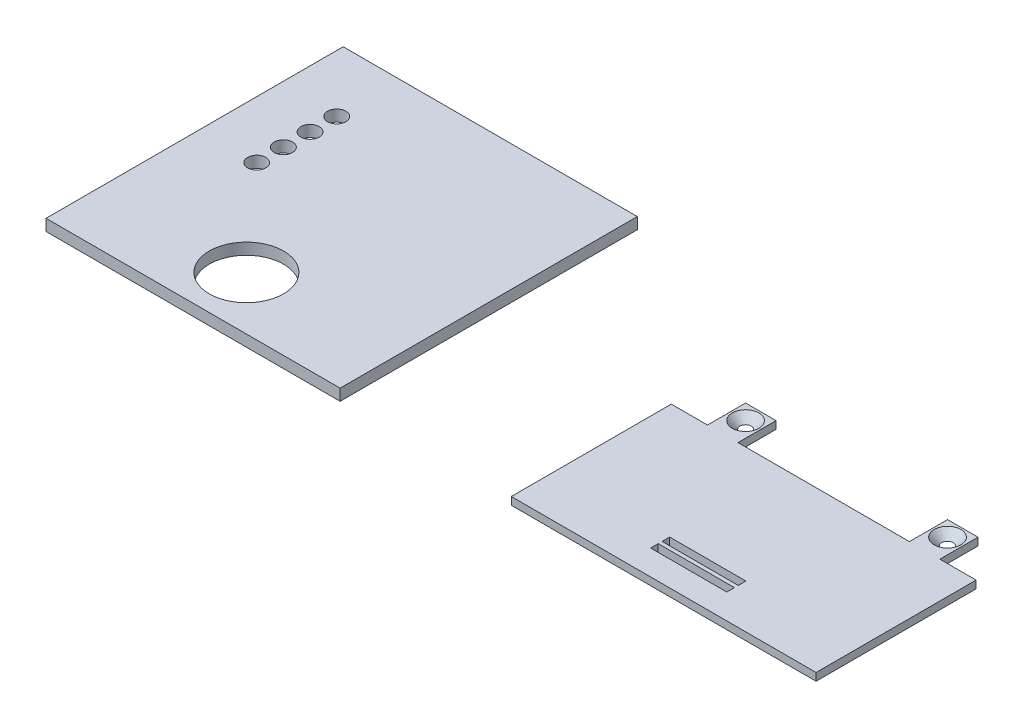
SolidWorks part; units mm, degrees
ref_plane "Front" through (0, 0, 0) normal (0, 0, 1) x (1, 0, 0)
ref_plane "Top" through (0, 0, 0) normal (0, 1, 0) x (1, 0, 0)
ref_plane "Right" through (0, 0, 0) normal (1, 0, 0) x (0, 0, -1)
sketch "Эскиз1" plane through (0, 0, 0) normal (0, 1, 0) x (1, 0, 0)
  line L1 (-158.1764, 86.5492) -> (-80.9764, 86.5492)
  line L2 (-158.1764, 86.5492) -> (-158.1764, 8.5492)
  line L3 (-158.1764, 8.5492) -> (-80.9764, 8.5492)
  line L4 (-80.9764, 86.5492) -> (-80.9764, 8.5492)
  dimension "D1" = 77.2
  dimension "D2" = 78
extrude "Бобышка-Вытянуть1" add sketch "Эскиз1" along normal blind 3
sketch "Эскиз2" plane through (0, 3, 0) normal (0, 1, 0) x (1, 0, 0)
  line L0 (-158.1764, 86.5492) -> (-158.1764, 8.5492) construction
  line L1 (-158.1764, 8.5492) -> (-80.9764, 8.5492) construction
  circle A0 centre (-119.5764, 22.5492) radius 9.75
  dimension "D1" = 38.6
  dimension "D2" = 14
extrude "Вырез-Вытянуть1" cut sketch "Эскиз2" along normal blind 87 and the other way blind 71
sketch "Эскиз3" plane through (0, 3, 0) normal (0, 1, 0) x (1, 0, 0)
  line L0 (-158.1764, 86.5492) -> (-158.1764, 8.5492) construction
  circle A0 centre (-143.1764, 48.8556) radius 2.4
  circle A1 centre (-143.1764, 55.8556) radius 2.4
  circle A2 centre (-138.1048, 0) radius 2.4
  circle A3 centre (-138.1048, 0) radius 2.4
  circle A4 centre (-143.1764, 69.8556) radius 2.4
  circle A5 centre (-143.1764, 62.8556) radius 2.4
  point P14 (0, 0)
  dimension "D1" = 15
  dimension "D2" = 15
  dimension "D3" = 7
  dimension "D4" = 15
  dimension "D5" = 7
  dimension "D6" = 15
  dimension "D7" = 7
extrude "Вырез-Вытянуть3" cut sketch "Эскиз3" against normal blind 207 and the other way blind 150 contours A4 | A5 | A1 | A0
sketch "Эскиз4" plane through (0, 0, 0) normal (0, 1, 0) x (1, 0, 0)
  line L1 (-36.8822, 61.3775) -> (43.1178, 61.3775)
  line L2 (-36.8822, 61.3775) -> (-36.8822, 9.3775)
  line L3 (-36.8822, 9.3775) -> (43.1178, 9.3775)
  line L4 (43.1178, 61.3775) -> (43.1178, 9.3775)
  dimension "D1" = 80
  dimension "D2" = 52
extrude "Бобышка-Вытянуть2" add sketch "Эскиз4" against normal blind 2 separate body
sketch "Эскиз5" plane through (0, 0, 0) normal (0, 1, 0) x (1, 0, 0)
  line L1 (-36.8822, 61.3775) -> (-27.3822, 61.3775)
  line L2 (-36.8822, 61.3775) -> (-36.8822, 51.3775)
  line L3 (-36.8822, 51.3775) -> (-27.3822, 51.3775)
  line L4 (-27.3822, 61.3775) -> (-27.3822, 51.3775)
  point P5 (-27.3822, 56.3775)
  dimension "D1" = 9.5
  dimension "D2" = 10
extrude "Вырез-Вытянуть4" cut sketch "Эскиз5" along normal blind 35 and the other way blind 32
sketch "Эскиз6" plane through (0, 0, 0) normal (0, 1, 0) x (1, 0, 0)
  line L0 (43.1178, 61.3775) -> (-27.3822, 61.3775) construction
  line L1 (-19.3822, 61.3775) -> (25.6178, 61.3775)
  line L2 (-19.3822, 61.3775) -> (-19.3822, 51.3775)
  line L3 (-19.3822, 51.3775) -> (25.6178, 51.3775)
  line L4 (25.6178, 61.3775) -> (25.6178, 51.3775)
  line L5 (-27.3822, 51.3775) -> (-27.3822, 61.3775) construction
  dimension "D1" = 8
  dimension "D2" = 10
  dimension "D3" = 45
extrude "Вырез-Вытянуть5" cut sketch "Эскиз6" against normal blind 45 and the other way blind 54
sketch "Эскиз7" plane through (0, 0, 0) normal (0, 1, 0) x (1, 0, 0)
  line L1 (43.1178, 61.3775) -> (33.6178, 61.3775)
  line L2 (43.1178, 61.3775) -> (43.1178, 51.3775)
  line L3 (43.1178, 51.3775) -> (33.6178, 51.3775)
  line L4 (33.6178, 61.3775) -> (33.6178, 51.3775)
  dimension "D1" = 10
  dimension "D2" = 9.5
extrude "Вырез-Вытянуть6" cut sketch "Эскиз7" against normal blind 67 and the other way blind 64
sketch "Эскиз8" plane through (0, 0, 0) normal (0, 1, 0) x (1, 0, 0)
  line L0 (-19.3822, 61.3775) -> (-27.3822, 61.3775) construction
  line L1 (-19.3822, 51.3775) -> (-19.3822, 61.3775) construction
  circle A0 centre (-23.3822, 57.3775) radius 1.5
  dimension "D1" = 4
  dimension "D2" = 4
extrude "Вырез-Вытянуть7" cut sketch "Эскиз8" against normal blind 30 and the other way blind 30
chamfer "Фаска1" distance 2 angle 45 1 edges at (-23.3822, 0, -55.8775)
sketch "Эскиз9" plane through (0, 0, 0) normal (0, 1, 0) x (1, 0, 0)
  line L0 (33.6178, 61.3775) -> (25.6178, 61.3775) construction
  line L1 (25.6178, 61.3775) -> (25.6178, 51.3775) construction
  circle A0 centre (29.6178, 57.3775) radius 1.5
  point P6 (29.6178, 57.3775)
  dimension "D1" = 4
  dimension "D2" = 4
extrude "Вырез-Вытянуть8" cut sketch "Эскиз9" against normal blind 33 and the other way blind 20
chamfer "Фаска2" distance 2 angle 45 1 edges at (29.6178, 0, -55.8775)
sketch "Эскиз10" plane through (0, 0, 0) normal (0, 1, 0) x (1, 0, 0)
  line L0 (-36.8822, 51.3775) -> (-36.8822, 9.3775) construction
  line L1 (-6.8822, 17.9462) -> (13.1178, 17.9462)
  line L2 (-6.8822, 17.9462) -> (-6.8822, 15.9462)
  line L3 (-6.8822, 15.9462) -> (13.1178, 15.9462)
  line L4 (13.1178, 17.9462) -> (13.1178, 15.9462)
  line L5 (-6.8822, 20.9462) -> (13.1178, 20.9462)
  line L6 (-6.8822, 20.9462) -> (-6.8822, 18.9462)
  line L7 (-6.8822, 18.9462) -> (13.1178, 18.9462)
  line L8 (13.1178, 20.9462) -> (13.1178, 18.9462)
  point P4 (13.1178, 16.9462)
  point P11 (13.1178, 19.9462)
  dimension "D1" = 20
  dimension "D2" = 2
  dimension "D3" = 30
  dimension "D4" = 30
  dimension "D5" = 1
  dimension "D6" = 2
extrude "Вырез-Вытянуть9" cut sketch "Эскиз10" against normal blind 2
move or copy body "Тело-Переместить/Копировать1" bodies to move or copy 111 placed by mates yes
